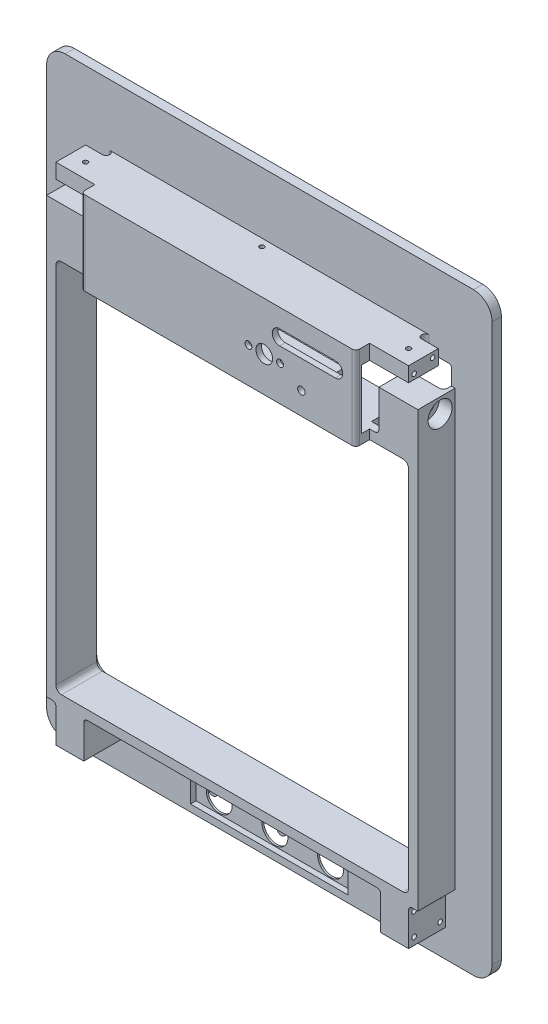
SolidWorks part; units mm, degrees
ref_plane "Front" through (0, 0, 0) normal (0, 0, 1) x (1, 0, 0)
ref_plane "Top" through (0, 0, 0) normal (0, 1, 0) x (1, 0, 0)
ref_plane "Right" through (0, 0, 0) normal (1, 0, 0) x (0, 0, -1)
sketch "Sketch1" plane through (0, 0, 0) normal (0, 0, 1) x (1, 0, 0)
  line L1 (0, 0) -> (240, 0)
  line L2 (0, 0) -> (0, 320)
  line L3 (0, 320) -> (240, 320)
  line L4 (240, 0) -> (240, 320)
  dimension "D1" = 240
  dimension "D2" = 320
extrude "Boss-Extrude1" add sketch "Sketch1" along normal blind 5
fillet "Fillet1" radius 10 4 edges at (240, 320, 2.5) (0, 320, 2.5) (0, 0, 2.5) (240, 0, 2.5)
sketch "Sketch2" plane through (0, 0, 5) normal (0, 0, 1) x (1, 0, 0)
  line L0 (120, 320) -> (120, 0) construction
  line L1 (230, 320) -> (10, 320) construction
  line L2 (10, 0) -> (230, 0) construction
  line L4 (215, 242) -> (25, 242)
  line L5 (215, 242) -> (215, 40)
  line L6 (215, 40) -> (25, 40)
  line L7 (25, 242) -> (25, 40)
  line L8 (215, 242) -> (25, 40) construction
  line L9 (215, 40) -> (25, 242) construction
  point P6 (120, 141)
  dimension "D1" = 202
  dimension "D2" = 40
  dimension "D3" = 190
extrude "Cut-Extrude1" cut sketch "Sketch2" against normal through all
ref_plane "Plane1" through (120, 0, 0) normal (1, 0, 0) x (0, 0, -1)
ref_plane "Plane2" through (0, 160, 0) normal (0, -1, 0) x (-1, 0, 0)
sketch "Sketch5" plane through (0, 0, 0) normal (0, 0, -1) x (-1, 0, 0)
  line L25 (-120, 37) -> (-120, 0) construction
  line L26 (-240, 10) -> (-240, 310) construction
  line L27 (-25, 40) -> (-215, 40) construction
  line L29 (-28, 274) -> (-212, 274)
  line L30 (-218, 268) -> (-218, 43)
  line L31 (-22, 43) -> (-22, 268)
  line L32 (-212, 37) -> (-28, 37)
  line L77 (-10, 0) -> (-230, 0) construction
  line L79 (0, 310) -> (0, 10) construction
  line L80 (-230, 320) -> (-10, 320) construction
  arc A24 (-22, 268) -> (-28, 274) centre (-28, 268) ccw
  arc A25 (-212, 274) -> (-218, 268) centre (-212, 268) ccw
  arc A26 (-218, 43) -> (-212, 37) centre (-212, 43) ccw
  arc A27 (-28, 37) -> (-22, 43) centre (-28, 43) ccw
  dimension "D1" = 6
  dimension "D5" = 46
  dimension "D3" = 22
  dimension "D7" = 22
  dimension "D4" = 46
  dimension "D2" = 3
extrude "Cut-Extrude3" cut sketch "Sketch5" against normal blind 3
sketch "Sketch6" plane through (0, 0, 5) normal (0, 0, 1) x (1, 0, 0)
  line L0 (215, 242) -> (25, 242) construction
  line L1 (199, 242) -> (41, 242)
  line L2 (199, 242) -> (199, 274)
  line L3 (199, 274) -> (41, 274)
  line L4 (41, 242) -> (41, 274)
  line L5 (197, 241) -> (197, 249) construction
  line L7 (43, 254) -> (43, 249) construction
  line L8 (28, 274) -> (212, 274) construction
  dimension "D1" = 2
  dimension "D3" = 2
extrude "Cut-Extrude4" cut sketch "Sketch6" against normal through all
sketch "Sketch7" plane through (0, 0, 5) normal (0, 0, 1) x (1, 0, 0)
  line L0 (230, 320) -> (10, 320) construction
  line L3 (215, 40) -> (215, 242)
  line L4 (25, 40) -> (215, 40)
  line L5 (25, 242) -> (25, 40)
  line L11 (199, 282) -> (41, 282)
  line L12 (41, 242) -> (25, 242)
  line L13 (41, 282) -> (41, 242)
  line L14 (199, 242) -> (199, 282)
  line L15 (215, 242) -> (199, 242)
  line L18 (240, 10) -> (240, 310) construction
  line L19 (0, 310) -> (0, 10) construction
  line L20 (10, 0) -> (230, 0) construction
  dimension "D1" = 25
  dimension "D2" = 25
  dimension "D3" = 40
  dimension "D4" = 242
  dimension "D6" = 158
  dimension "D5" = 38
extrude "Extrude-Thin1" add sketch "Sketch7" along normal blind 20 thin
sketch "Sketch8" plane through (204, 0, 0) normal (1, 0, 0) x (0, 0, -1)
  line L0 (-5, 247) -> (-5, 287) construction
  line L1 (-25, 247) -> (-5, 247) construction
  circle A0 centre (-13, 261) radius 6.5
  dimension "D1" = 8
  dimension "D2" = 14
  dimension "D3" = 13
extrude "Cut-Extrude5" cut sketch "Sketch8" against normal offset from surface (2 mm away) 3 up to face at (199, 266, 11)
sketch "Sketch9" plane through (202, 0, 0) normal (1, 0, 0) x (0, 0, -1)
  circle A0 centre (-13, 261) radius 3.75
  circle A1 centre (-13, 261) radius 6.5 construction
  dimension "D1" = 7.5
extrude "Cut-Extrude6" cut sketch "Sketch9" against normal up to vertex (3 mm away)
sketch "Sketch10" plane through (204, 0, 0) normal (1, 0, 0) x (0, 0, -1)
  line L0 (-5, 264.5) -> (-9.2, 269)
  line L1 (-5, 10) -> (-5, 310) construction
  line L2 (-9.2, 269) -> (-25, 269)
  line L4 (-25, 269) -> (-25, 282)
  line L5 (-25, 282) -> (-5, 282)
  line L6 (-5, 282) -> (-5, 264.5)
  line L8 (-25, 247) -> (-25, 287) construction
  line L9 (-25, 282) -> (-5, 282) construction
  dimension "D2" = 17.5
  dimension "D3" = 13
  dimension "D4" = 15.8
extrude "Cut-Extrude7" cut sketch "Sketch10" against normal through all
sketch "Sketch11" plane through (0, 0, 5) normal (0, 0, 1) x (1, 0, 0)
  line L0 (217, 42) -> (217, 270) construction
  line L1 (218, 279) -> (22, 279)
  line L2 (218, 279) -> (218, 247)
  line L3 (218, 247) -> (22, 247)
  line L4 (22, 279) -> (22, 247)
  line L5 (23, 270) -> (23, 42) construction
  line L6 (36, 282) -> (204, 282) construction
  line L7 (220, 247) -> (204, 247) construction
  dimension "D1" = 1
  dimension "D2" = 1
  dimension "D3" = 3
extrude "Cut-Extrude8" cut sketch "Sketch11" against normal blind 12
sketch "Sketch12" plane through (0, 0, 25) normal (0, 0, 1) x (1, 0, 0)
  line L0 (41, 269) -> (41, 242) construction
  line L1 (199, 242) -> (41, 242)
  line L2 (199, 242) -> (199, 247)
  line L3 (199, 247) -> (41, 247)
  line L4 (41, 242) -> (41, 247)
  line L5 (36, 247) -> (20, 247) construction
extrude "Boss-Extrude2" add sketch "Sketch12" against normal up to surface (22 mm away) up to face at (120, 156.6796, 3)
sketch "Sketch13" plane through (0, 0, 3) normal (0, 0, -1) x (-1, 0, 0)
  line L0 (-215, 242) -> (-25, 242) construction
  line L1 (-42, 242) -> (-49, 242)
  line L2 (-42, 242) -> (-42, 247)
  line L3 (-42, 247) -> (-49, 247)
  line L4 (-49, 242) -> (-49, 247)
  line L5 (-218, 247) -> (-22, 247) construction
  line L6 (-48, 241) -> (-48, 247) construction
  line L7 (-74.3, 242) -> (-81.3, 242)
  line L8 (-74.3, 242) -> (-74.3, 247)
  line L9 (-74.3, 247) -> (-81.3, 247)
  line L10 (-81.3, 242) -> (-81.3, 247)
  line L11 (-158.7, 242) -> (-165.7, 242)
  line L12 (-158.7, 242) -> (-158.7, 247)
  line L13 (-158.7, 247) -> (-165.7, 247)
  line L14 (-165.7, 242) -> (-165.7, 247)
  line L15 (-191, 242) -> (-198, 242)
  line L16 (-191, 242) -> (-191, 247)
  line L17 (-191, 247) -> (-198, 247)
  line L18 (-198, 242) -> (-198, 247)
  line L19 (-43, 273) -> (-43, 241) construction
  line L20 (-197, 241) -> (-197, 273) construction
  line L21 (-192, 247) -> (-192, 241) construction
  line L22 (-164.7, 241) -> (-164.7, 247) construction
  line L23 (-159.7, 268) -> (-159.7, 241) construction
  line L24 (-80.3, 241) -> (-80.3, 268) construction
  line L25 (-75.3, 247) -> (-75.3, 241) construction
  dimension "D1" = 1
  dimension "D2" = 1
  dimension "D3" = 1
  dimension "D4" = 1
  dimension "D5" = 1
  dimension "D6" = 1
  dimension "D7" = 1
  dimension "D8" = 1
extrude "Cut-Extrude9" cut sketch "Sketch13" against normal blind 18
sketch "Sketch15" plane through (204, 0, 0) normal (1, 0, 0) x (0, 0, -1)
  line L5 (-5, 247) -> (-5, 264.5)
  line L6 (-5, 264.5) -> (-9.2, 269)
  line L7 (-9.2, 269) -> (-25, 269)
  line L8 (-25, 269) -> (-25, 247)
  line L9 (-25, 247) -> (-5, 247)
  line L10 (-5, 247) -> (-5, 264.5)
  line L11 (-5, 264.5) -> (-9.2, 269)
  line L13 (-25, 269) -> (-25, 247)
  line L14 (-25, 247) -> (-5, 247)
  line L16 (-9.2, 269) -> (-25, 269)
  circle A0 centre (-13, 261) radius 6.5 construction
  circle A1 centre (-13, 261) radius 6.5
  dimension "D1" = 0
extrude "Boss-Extrude4" add sketch "Sketch15" along normal up to surface (16 mm away) up to face at (220, 141, 15)
sketch "Sketch16" plane through (220, 0, 0) normal (1, 0, 0) x (0, 0, -1)
  line L0 (-5, 264.5) -> (-5, 269)
  line L1 (-5, 269) -> (-9.2, 269)
  line L2 (-9.2, 269) -> (-5, 264.5)
  line L3 (-5, 35) -> (-5, 264.5) construction
extrude "Boss-Extrude5" add sketch "Sketch16" against normal up to surface (2 mm away) up to face at (218, 200.3571, 3)
sketch "Sketch17" plane through (36, 0, 0) normal (-1, 0, 0) x (0, 0, 1)
  line L5 (25, 269) -> (9.2, 269)
  line L6 (9.2, 269) -> (5, 264.5)
  line L7 (5, 264.5) -> (5, 247)
  line L8 (5, 247) -> (25, 247)
  line L9 (25, 247) -> (25, 269)
  line L10 (25, 269) -> (9.2, 269)
  line L11 (9.2, 269) -> (5, 264.5)
  line L12 (5, 264.5) -> (5, 247)
  line L13 (5, 247) -> (25, 247)
  line L14 (25, 247) -> (25, 269)
  dimension "D1" = 0
extrude "Boss-Extrude6" add sketch "Sketch17" along normal up to surface (16 mm away) up to face at (20, 141, 15)
sketch "Sketch18" plane through (20, 0, 0) normal (-1, 0, 0) x (0, 0, 1)
  line L0 (9.2, 269) -> (5, 269)
  line L1 (5, 269) -> (5, 264.5)
  line L2 (5, 264.5) -> (9.2, 269)
  line L3 (5, 264.5) -> (9.2, 269) construction
  line L4 (5, 264.5) -> (5, 35) construction
extrude "Boss-Extrude7" add sketch "Sketch18" against normal up to surface (2 mm away) up to face at (22, 200.3571, 3)
sketch "Sketch19" plane through (0, 242, 0) normal (0, -1, 0) x (1, 0, 0)
  line L0 (215, 25) -> (25, 25) construction
  line L1 (46, 25) -> (194, 25)
  line L2 (46, 25) -> (46, 32.45)
  line L3 (46, 32.45) -> (194, 32.45)
  line L4 (194, 25) -> (194, 32.45)
  line L5 (132.5523, 32.45) -> (156.8523, 32.45) construction
  line L10 (42, 21) -> (42, 3) construction
  line L11 (198, 21) -> (198, 3) construction
  dimension "D1" = 4
  dimension "D2" = 4
extrude "Boss-Extrude8" add sketch "Sketch19" against normal up to surface (5 mm away)
sketch "Sketch20" plane through (0, 247, 0) normal (0, 1, 0) x (1, 0, 0)
  line L0 (194, -32.45) -> (194, -25) construction
  line L1 (46, -32.45) -> (194, -32.45)
  line L2 (46, -32.45) -> (46, -29.45)
  line L3 (46, -29.45) -> (194, -29.45)
  line L4 (194, -32.45) -> (194, -29.45)
  dimension "D1" = 3
extrude "Boss-Extrude9" add sketch "Sketch20" along normal up to surface (40 mm away) up to face at (120, 287, 15)
sketch "Sketch22" plane through (0, 0, 29.45) normal (0, 0, -1) x (-1, 0, 0)
  line L0 (-194, 287) -> (-194, 247) construction
  line L1 (-46, 287) -> (-194, 287)
  line L2 (-46, 287) -> (-46, 282)
  line L3 (-46, 282) -> (-194, 282)
  line L4 (-194, 287) -> (-194, 282)
  line L5 (-204, 282) -> (-36, 282) construction
extrude "Boss-Extrude10" add sketch "Sketch22" along normal up to surface (4.45 mm away) up to face at (120, 284.5, 25)
sketch "Sketch23" plane through (0, 0, 32.45) normal (0, 0, 1) x (1, 0, 0)
  circle A0 centre (144.7023, 261) radius 4.5
  circle A1 centre (144.7023, 261) radius 3.5 construction
  dimension "D1" = 1
extrude "Cut-Extrude10" cut sketch "Sketch23" against normal up to surface (3 mm away) up to face at (120, 264.5, 29.45)
sketch "Sketch24" plane through (0, 0, 32.45) normal (0, 0, 1) x (1, 0, 0)
  circle A0 centre (136.2023, 261) radius 1.85
  circle A1 centre (153.2023, 261) radius 1.85
  circle A2 centre (153.2023, 261) radius 1.25 construction
  circle A3 centre (136.2023, 261) radius 1.25 construction
  dimension "D1" = 0.6
  dimension "D2" = 0.6
extrude "Cut-Extrude11" cut sketch "Sketch24" against normal blind 4
sketch "Sketch25" plane through (0, 0, 29.45) normal (0, 0, -1) x (-1, 0, 0)
  circle A0 centre (-136.2023, 261) radius 3.35
  circle A1 centre (-153.2023, 261) radius 3.35
  circle A2 centre (-136.2023, 261) radius 1.85 construction
  dimension "D1" = 1.5
extrude "Cut-Extrude12" cut sketch "Sketch25" against normal blind 1
sketch "Sketch27" plane through (0, 0, 25) normal (0, 0, 1) x (1, 0, 0)
  line L1 (204, 287) -> (194, 287)
  line L2 (204, 287) -> (204, 242)
  line L3 (204, 242) -> (194, 242)
  line L4 (194, 287) -> (194, 242)
  line L5 (46, 242) -> (36, 242)
  line L6 (46, 242) -> (46, 287)
  line L7 (46, 287) -> (36, 287)
  line L8 (36, 242) -> (36, 287)
sketch "Sketch28" plane through (0, 282, 0) normal (0, -1, 0) x (1, 0, 0)
  line L8 (36, 5) -> (204, 5)
  line L9 (204, 5) -> (204, 25)
  line L10 (204, 25) -> (194, 25)
  line L11 (204, 25) -> (194, 25)
  line L12 (194, 29.45) -> (46, 29.45)
  line L14 (194, 25) -> (194, 29.45)
  line L15 (36, 25) -> (36, 5)
  line L16 (36, 5) -> (204, 5)
  line L17 (204, 5) -> (204, 25)
  line L20 (194, 29.45) -> (46, 29.45)
  line L23 (36, 25) -> (36, 5)
  line L24 (194, 25) -> (194, 29.45)
  line L26 (46, 29.45) -> (46, 25)
  line L27 (46, 29.45) -> (46, 25)
  line L28 (46, 25) -> (36, 25)
  line L29 (46, 25) -> (36, 25)
  dimension "D1" = 0
extrude "Boss-Extrude12" add sketch "Sketch28" along normal up to surface (3 mm away) up to face at (120, 279, 2.5)
sketch "Sketch29" plane through (20, 0, 0) normal (-1, 0, 0) x (0, 0, 1)
  circle A0 centre (13, 261) radius 6.5 construction
  circle A1 centre (13, 261) radius 6.5
extrude "Cut-Extrude13" cut sketch "Sketch29" against normal offset from surface (18 mm away) 3 up to face at (41, 259.3, 13.84)
sketch "Sketch30" plane through (38, 0, 0) normal (-1, 0, 0) x (0, 0, 1)
  circle A0 centre (13, 261) radius 3.75 construction
  circle A1 centre (13, 261) radius 3.75
extrude "Cut-Extrude14" cut sketch "Sketch30" against normal blind 13
fillet "Fillet4" radius 3 2 edges at (25, 242, 14) (215, 242, 14)
sketch "Sketch32" plane through (0, 0, 5) normal (0, 0, 1) x (1, 0, 0)
  circle A1 centre (31.0626, 282) radius 1.25
  circle A2 centre (208.9374, 282) radius 1.25
  circle A3 centre (31.0626, 282) radius 1.4 construction
  circle A4 centre (208.9374, 282) radius 1.4 construction
  dimension "D1" = 2.5
hole_wizard "M2.5 Tapped Hole2" positions "3DSketch2" profile "Sketch33" tap size "M2.5" standard "ISO"
sketch3d "3DSketch2"
  point P3 (31.0626, 282, 5)
  point P6 (208.9374, 282, 5)
sketch "Sketch33" plane through (31.0626, 282, 5) normal (1, 0, 0) x (0, -1, 0)
  line L0 (0, 0) -> (0, 4.6159)
  line L1 (0, 4.6159) -> (1.025, 4)
  line L2 (1.025, 4) -> (1.025, 0)
  line L5 (1.025, 0) -> (0, 0)
  line L10 (0, 4.6159) -> (-1.025, 4) construction
  line L11 (0, -6.35) -> (0, 107.95) construction
  dimension "Tap Drill Dia." = 2.05
  dimension "Tap Drill Depth" = 4
  dimension "Drill Angle" = 118
cosmetic thread "Hole Thread6" parameters "D1"=3, "D2"=2.5
cosmetic thread "Hole Thread7" parameters "D1"=3, "D2"=2.5
sketch "Sketch34" plane through (0, 0, 29.45) normal (0, 0, -1) x (-1, 0, 0)
  line L0 (-183, 273) -> (-153, 273) construction
  line L1 (-183, 277) -> (-153, 277)
  line L2 (-183, 269) -> (-153, 269)
  line L3 (-46, 279) -> (-194, 279) construction
  line L4 (-240, 10) -> (-240, 310) construction
  arc A0 (-183, 277) -> (-183, 269) centre (-183, 273) ccw
  arc A1 (-153, 269) -> (-153, 277) centre (-153, 273) ccw
  point P2 (-168, 273)
  dimension "D4" = 57
  dimension "D1" = 8
  dimension "D2" = 30
  dimension "D3" = 6
extrude "Cut-Extrude15" cut sketch "Sketch34" against normal through all
sketch "Sketch35" plane through (202, 0, 0) normal (1, 0, 0) x (0, 0, -1)
  circle A0 centre (-13, 261) radius 3.75 construction
  circle A1 centre (-13, 261) radius 6.5
  circle A2 centre (-13, 261) radius 6.5
  circle A3 centre (-13, 261) radius 3.75
  dimension "D1" = 0
extrude "Boss-Extrude13" add sketch "Sketch35" along normal offset from surface (11 mm away) 7 up to face at (220, 152, 15)
sketch "Sketch36" plane through (38, 0, 0) normal (-1, 0, 0) x (0, 0, 1)
  circle A0 centre (13, 261) radius 3.75 construction
  circle A1 centre (13, 261) radius 6.5
  circle A2 centre (13, 261) radius 6.5
  circle A3 centre (13, 261) radius 3.75
  dimension "D1" = 0
extrude "Boss-Extrude14" add sketch "Sketch36" along normal offset from surface (11 mm away) 7
sketch "Sketch37" plane through (0, 0, 5) normal (0, 0, 1) x (1, 0, 0)
  line L0 (20, 35) -> (220, 35) construction
  line L1 (215, 15) -> (200, 15)
  line L2 (215, 15) -> (215, 35)
  line L3 (215, 35) -> (200, 35)
  line L4 (200, 15) -> (200, 35)
  line L6 (25, 15) -> (40, 15)
  line L7 (25, 15) -> (25, 35)
  line L8 (25, 35) -> (40, 35)
  line L9 (40, 15) -> (40, 35)
  dimension "D1" = 15
extrude "Boss-Extrude15" add sketch "Sketch37" along normal up to surface (20 mm away) up to face at (199, 283, 25)
sketch "Sketch38" plane through (25, 0, 0) normal (-1, 0, 0) x (0, 0, 1)
  circle A0 centre (8, 19) radius 1.5
  circle A1 centre (8, 31) radius 1.5
  circle A2 centre (22, 19) radius 1.5
  circle A3 centre (22, 31) radius 1.5
  circle A4 centre (8, 19) radius 1.65 construction
  circle A5 centre (8, 31) radius 1.65 construction
  circle A6 centre (22, 19) radius 1.65 construction
  circle A7 centre (22, 31) radius 1.65 construction
  dimension "D1" = 3
hole_wizard "M3 Tapped Hole1" positions "3DSketch3" profile "Sketch39" tap size "M3" standard "ISO"
sketch3d "3DSketch3"
  point P0 (25, 19, 8)
  point P3 (25, 31, 8)
  point P6 (25, 19, 22)
  point P9 (25, 31, 22)
sketch "Sketch39" plane through (25, 19, 8) normal (0, 1, 0) x (0, 0, 1)
  line L0 (0, 0) -> (0, 12.2511)
  line L1 (0, 12.2511) -> (1.25, 11.5)
  line L2 (1.25, 11.5) -> (1.25, 0)
  line L5 (1.25, 0) -> (0, 0)
  line L10 (0, 12.2511) -> (-1.25, 11.5) construction
  line L11 (0, -6.35) -> (0, 107.95) construction
  dimension "Tap Drill Dia." = 2.5
  dimension "Tap Drill Depth" = 11.5
  dimension "Drill Angle" = 118
cosmetic thread "Hole Thread8" parameters "D1"=10, "D2"=3
cosmetic thread "Hole Thread9" parameters "D1"=10, "D2"=3
cosmetic thread "Hole Thread10" parameters "D1"=10, "D2"=3
cosmetic thread "Hole Thread11" parameters "D1"=10, "D2"=3
sketch "Sketch40" plane through (215, 0, 0) normal (1, 0, 0) x (0, 0, -1)
  circle A0 centre (-8, 31) radius 1.5
  circle A1 centre (-8, 19) radius 1.5
  circle A2 centre (-22, 31) radius 1.5
  circle A3 centre (-22, 19) radius 1.5
  dimension "D1" = 3
hole_wizard "M3 Tapped Hole2" positions "3DSketch4" profile "Sketch41" tap size "M3" standard "ISO"
sketch3d "3DSketch4"
  point P0 (215, 31, 8)
  point P3 (215, 19, 8)
  point P6 (215, 19, 22)
  point P9 (215, 31, 22)
sketch "Sketch41" plane through (215, 31, 8) normal (0, 1, 0) x (0, 0, -1)
  line L0 (0, 0) -> (0, 12.2511)
  line L1 (0, 12.2511) -> (1.25, 11.5)
  line L2 (1.25, 11.5) -> (1.25, 0)
  line L5 (1.25, 0) -> (0, 0)
  line L10 (0, 12.2511) -> (-1.25, 11.5) construction
  line L11 (0, -6.35) -> (0, 107.95) construction
  dimension "Tap Drill Dia." = 2.5
  dimension "Tap Drill Depth" = 11.5
  dimension "Drill Angle" = 118
cosmetic thread "Hole Thread12" parameters "D1"=10, "D2"=3
cosmetic thread "Hole Thread13" parameters "D1"=10, "D2"=3
cosmetic thread "Hole Thread14" parameters "D1"=10, "D2"=3
cosmetic thread "Hole Thread15" parameters "D1"=10, "D2"=3
sketch "Sketch42" plane through (0, 0, 29.45) normal (0, 0, -1) x (-1, 0, 0)
  line L0 (-230, 320) -> (-10, 320) construction
  line L1 (-240, 10) -> (-240, 310) construction
  circle A0 centre (-164.7, 254) radius 2
  dimension "D1" = 4
  dimension "D2" = 66
  dimension "D3" = 75.3
extrude "Cut-Extrude16" cut sketch "Sketch42" against normal blind 10
fillet "Fillet7" radius 2 4 edges at (25, 35, 15) (40, 35, 15) (200, 35, 15) (215, 35, 15)
fillet "Fillet8" radius 3 2 edges at (25, 40, 14) (215, 40, 14)
fillet "Fillet9" radius 1 4 edges at (218, 279, 2.5) (22, 279, 2.5) (218, 247, 4) (22, 247, 4)
fillet "Fillet10" radius 2 4 edges at (41, 247, 15) (199, 247, 15) (218, 266.75, 7.1) (22, 266.75, 7.1)
fillet "Fillet11" radius 2 2 edges at (194, 264.5, 32.45) (46, 264.5, 32.45)
sketch "Sketch43" plane through (36, 0, 0) normal (-1, 0, 0) x (0, 0, 1)
  line L0 (25, 287) -> (5, 287) construction
  line L1 (25, 279) -> (9, 279)
  line L2 (25, 279) -> (25, 287)
  line L3 (25, 287) -> (9, 287)
  line L4 (9, 279) -> (9, 287)
  line L6 (5, 287) -> (5, 279) construction
  dimension "D1" = 4
extrude "Boss-Extrude16" add sketch "Sketch43" along normal up to surface (11 mm away)
sketch "Sketch44" plane through (204, 0, 0) normal (1, 0, 0) x (0, 0, -1)
  line L4 (-25, 287) -> (-25, 279)
  line L5 (-9, 287) -> (-25, 287)
  line L6 (-9, 279) -> (-9, 287)
  line L7 (-25, 279) -> (-9, 279)
  line L8 (-25, 287) -> (-25, 279)
  line L9 (-9, 287) -> (-25, 287)
  line L10 (-9, 279) -> (-9, 287)
  line L11 (-25, 279) -> (-9, 279)
  dimension "D1" = 0
extrude "Boss-Extrude17" add sketch "Sketch44" along normal up to surface (11 mm away)
fillet "Fillet12" radius 2 4 edges at (204, 283, 9) (204, 283, 5) (36, 283, 9) (36, 283, 5)
sketch "Sketch45" plane through (215, 0, 0) normal (1, 0, 0) x (0, 0, -1)
  circle A0 centre (-12, 284.25) radius 1.5
  circle A1 centre (-22, 281.75) radius 1.5
  dimension "D1" = 3
hole_wizard "M3 Tapped Hole3" positions "3DSketch5" profile "Sketch46" tap size "M3" standard "ISO"
sketch3d "3DSketch5"
  point P0 (215, 284.25, 12)
  point P3 (215, 281.75, 22)
sketch "Sketch46" plane through (215, 284.25, 12) normal (0, 1, 0) x (0, 0, -1)
  line L0 (0, 0) -> (0, 12.7511)
  line L1 (0, 12.7511) -> (1.25, 12)
  line L2 (1.25, 12) -> (1.25, 0)
  line L5 (1.25, 0) -> (0, 0)
  line L10 (0, 12.7511) -> (-1.25, 12) construction
  line L11 (0, -6.35) -> (0, 107.95) construction
  dimension "Tap Drill Dia." = 2.5
  dimension "Tap Drill Depth" = 12
  dimension "Drill Angle" = 118
cosmetic thread "Hole Thread16" parameters "D1"=10, "D2"=3
cosmetic thread "Hole Thread17" parameters "D1"=10, "D2"=3
sketch "Sketch47" plane through (25, 0, 0) normal (-1, 0, 0) x (0, 0, 1)
  circle A0 centre (12, 284.25) radius 1.5
  circle A1 centre (22, 281.75) radius 1.5
  dimension "D1" = 3
hole_wizard "M3 Tapped Hole4" positions "3DSketch6" profile "Sketch48" tap size "M3" standard "ISO"
sketch3d "3DSketch6"
  point P0 (25, 284.25, 12)
  point P3 (25, 281.75, 22)
sketch "Sketch48" plane through (25, 284.25, 12) normal (0, 1, 0) x (0, 0, 1)
  line L0 (0, 0) -> (0, 12.7511)
  line L1 (0, 12.7511) -> (1.25, 12)
  line L2 (1.25, 12) -> (1.25, 0)
  line L5 (1.25, 0) -> (0, 0)
  line L10 (0, 12.7511) -> (-1.25, 12) construction
  line L11 (0, -6.35) -> (0, 107.95) construction
  dimension "Tap Drill Dia." = 2.5
  dimension "Tap Drill Depth" = 12
  dimension "Drill Angle" = 118
cosmetic thread "Hole Thread18" parameters "D1"=10, "D2"=3
cosmetic thread "Hole Thread19" parameters "D1"=10, "D2"=3
sketch "Sketch49" plane through (0, 0, 5) normal (0, 0, 1) x (1, 0, 0)
  circle A0 centre (138.5, 28) radius 2.5
  circle A1 centre (101.5, 28) radius 2.5
  arc A2 (138.5, 24.25) -> (138.5, 31.75) centre (138.5, 28) ccw construction
  arc A3 (101.5, 31.75) -> (101.5, 24.25) centre (101.5, 28) ccw construction
  dimension "D1" = 5
extrude "Boss-Extrude18" add sketch "Sketch49" along normal up to surface (12 mm away)
sketch "Sketch50" plane through (0, 0, 5) normal (0, 0, 1) x (1, 0, 0)
  line L1 (133.75, 24.75) -> (126.25, 24.75)
  line L2 (133.75, 24.75) -> (133.75, 31.25)
  line L3 (133.75, 31.25) -> (126.25, 31.25)
  line L4 (126.25, 24.75) -> (126.25, 31.25)
  line L5 (122.25, 24.75) -> (106.25, 24.75)
  line L6 (122.25, 24.75) -> (122.25, 31.25)
  line L7 (122.25, 31.25) -> (106.25, 31.25)
  line L8 (106.25, 24.75) -> (106.25, 31.25)
extrude "Cut-Extrude17" cut sketch "Sketch50" against normal through all
fillet "Fillet13" radius 1 8 edges at (122.25, 24.75, 2.5) (122.25, 31.25, 2.5) (106.25, 31.25, 2.5) (106.25, 24.75, 2.5) (126.25, 24.75, 2.5) (126.25, 31.25, 2.5) (133.75, 31.25, 2.5) (133.75, 24.75, 2.5)
sketch "Sketch51" plane through (0, 0, 17) normal (0, 0, 1) x (1, 0, 0)
  circle A0 centre (138.5, 28) radius 1.25
  circle A1 centre (101.5, 28) radius 1.25
  dimension "D1" = 2.5
hole_wizard "M2.5 Tapped Hole3" positions "3DSketch7" profile "Sketch52" tap size "M2.5" standard "ISO"
sketch3d "3DSketch7"
  point P0 (138.5, 28, 17)
  point P3 (101.5, 28, 17)
sketch "Sketch52" plane through (138.5, 28, 17) normal (1, 0, 0) x (0, -1, 0)
  line L0 (0, 0) -> (0, 6.9659)
  line L1 (0, 6.9659) -> (1.025, 6.35)
  line L2 (1.025, 6.35) -> (1.025, 0)
  line L5 (1.025, 0) -> (0, 0)
  line L10 (0, 6.9659) -> (-1.025, 6.35) construction
  line L11 (0, -6.35) -> (0, 107.95) construction
  dimension "Tap Drill Dia." = 2.05
  dimension "Tap Drill Depth" = 6.35
  dimension "Drill Angle" = 118
cosmetic thread "Hole Thread20" parameters "D1"=5, "D2"=2.5
cosmetic thread "Hole Thread21" parameters "D1"=5, "D2"=2.5
sketch "Sketch53" plane through (0, 0, 5) normal (0, 0, 1) x (1, 0, 0)
  line L1 (162.5, 3.75) -> (77.5, 3.75)
  line L2 (162.5, 3.75) -> (162.5, 23.75)
  line L3 (162.5, 23.75) -> (77.5, 23.75)
  line L4 (77.5, 3.75) -> (77.5, 23.75)
extrude "Cut-Extrude18" cut sketch "Sketch53" against normal blind 3
sketch "Sketch54" plane through (0, 0, 2) normal (0, 0, 1) x (1, 0, 0)
  line L0 (122.4, 22.75) -> (122.4, 17.95) construction
  line L1 (122.4, 17.95) -> (117.6, 17.95) construction
  line L2 (122.4, 17.95) -> (122.4, 22.75) construction
  line L3 (122.4, 22.75) -> (117.6, 22.75) construction
  line L4 (117.6, 17.95) -> (117.6, 22.75) construction
  line L5 (122.4, 17.95) -> (117.6, 17.95) construction
  line L6 (117.6, 17.95) -> (117.6, 22.75) construction
  line L7 (117.6, 22.75) -> (122.4, 22.75) construction
  line L8 (122.9, 23.25) -> (117.1, 23.25)
  line L9 (117.1, 17.45) -> (117.1, 23.25)
  line L10 (122.9, 17.45) -> (117.1, 17.45)
  line L11 (122.9, 17.45) -> (122.9, 23.25)
  dimension "D1" = 0.5
extrude "Cut-Extrude19" cut sketch "Sketch54" against normal through all
fillet "Fillet14" radius 1 2 edges at (117.1, 23.25, 1) (122.9, 23.25, 1)
sketch "Sketch55" plane through (0, 0, 2) normal (0, 0, 1) x (1, 0, 0)
  circle A0 centre (150, 11.25) radius 7
  circle A1 centre (120, 11.25) radius 7
  circle A2 centre (90, 11.25) radius 7
  dimension "D1" = 14
extrude "Cut-Extrude20" cut sketch "Sketch55" against normal through all
fillet "Fillet15" radius 1 2 edges at (117.1, 17.621, 1) (122.9, 17.621, 1)
sketch "Sketch56" plane through (0, 0, 0) normal (0, 0, -1) x (-1, 0, 0)
  line L0 (-120, 0) -> (-120, 37) construction
  line L1 (-10, 0) -> (-230, 0) construction
  line L2 (-212, 37) -> (-28, 37) construction
  line L3 (-160, 18.5) -> (-80, 18.5) construction
  line L4 (-160, 34) -> (-80, 34)
  line L5 (-160, 3) -> (-80, 3)
  arc A0 (-160, 34) -> (-160, 3) centre (-160, 18.5) ccw
  arc A1 (-80, 3) -> (-80, 34) centre (-80, 18.5) ccw
  point P8 (-120, 18.5)
  dimension "D1" = 80
  dimension "D2" = 3
  dimension "D3" = 3
extrude "Cut-Extrude21" cut sketch "Sketch56" against normal blind 1
sketch "Sketch57" plane through (0, 287, 0) normal (0, 1, 0) x (1, 0, 0)
  line L0 (25, -17) -> (215, -17) construction
  line L1 (25, -25) -> (25, -9) construction
  line L3 (215, -9) -> (215, -25) construction
  line L4 (120, -17) -> (120, -5) construction
  line L5 (206, -5) -> (34, -5) construction
  circle A0 centre (33, -17) radius 1.5
  circle A1 centre (120, -9) radius 1.5
  circle A2 centre (207, -17) radius 1.5
  dimension "D1" = 3
  dimension "D2" = 8
  dimension "D3" = 8
  dimension "D4" = 8
hole_wizard "M3 Tapped Hole5" positions "3DSketch8" profile "Sketch58" tap size "M3" standard "ISO"
sketch3d "3DSketch8"
  point P0 (33, 287, 17)
  point P3 (120, 287, 9)
  point P6 (207, 287, 17)
sketch "Sketch58" plane through (33, 287, 17) normal (1, 0, 0) x (0, 0, 1)
  line L0 (0, 0) -> (0, 10.2511)
  line L1 (0, 10.2511) -> (1.25, 9.5)
  line L2 (1.25, 9.5) -> (1.25, 0)
  line L5 (1.25, 0) -> (0, 0)
  line L10 (0, 10.2511) -> (-1.25, 9.5) construction
  line L11 (0, -6.35) -> (0, 107.95) construction
  dimension "Tap Drill Dia." = 2.5
  dimension "Tap Drill Depth" = 9.5
  dimension "Drill Angle" = 118
cosmetic thread "Hole Thread22" parameters "D1"=8, "D2"=3
cosmetic thread "Hole Thread23" parameters "D1"=8, "D2"=3
cosmetic thread "Hole Thread24" parameters "D1"=8, "D2"=3
sketch "Sketch59" plane through (0, 15, 0) normal (0, -1, 0) x (1, 0, 0)
  line L0 (215, 15) -> (200, 15) construction
  line L1 (215, 25) -> (215, 5) construction
  line L2 (200, 25) -> (200, 5) construction
  line L3 (40, 15) -> (25, 15) construction
  line L4 (40, 25) -> (40, 5) construction
  line L5 (25, 25) -> (25, 5) construction
  circle A0 centre (207.5, 15) radius 1.5
  circle A1 centre (32.5, 15) radius 1.5
  dimension "D1" = 3
hole_wizard "M3 Tapped Hole6" positions "3DSketch9" profile "Sketch60" tap size "M3" standard "ISO"
sketch3d "3DSketch9"
  point P0 (207.5, 15, 15)
  point P3 (32.5, 15, 15)
sketch "Sketch60" plane through (207.5, 15, 15) normal (1, 0, 0) x (0, 0, -1)
  line L0 (0, 0) -> (0, 8.2511)
  line L1 (0, 8.2511) -> (1.25, 7.5)
  line L2 (1.25, 7.5) -> (1.25, 0)
  line L5 (1.25, 0) -> (0, 0)
  line L10 (0, 8.2511) -> (-1.25, 7.5) construction
  line L11 (0, -6.35) -> (0, 107.95) construction
  dimension "Tap Drill Dia." = 2.5
  dimension "Tap Drill Depth" = 7.5
  dimension "Drill Angle" = 118
cosmetic thread "Hole Thread25" parameters "D1"=6, "D2"=3
cosmetic thread "Hole Thread26" parameters "D1"=6, "D2"=3
equation "\"D7@Sketch5\"=\"D3@Sketch5\""
equation "\"D2@Sketch7\"=\"D1@Sketch7\""
equation "\"D2@Sketch13\"=\"D1@Sketch13\""
equation "\"D4@Sketch13\"=\"D3@Sketch13\""
equation "\"D6@Sketch13\"=\"D5@Sketch13\""
equation "\"D8@Sketch13\"=\"D7@Sketch13\""
equation "\"D3@Sketch57\"=\"D2@Sketch57\""
